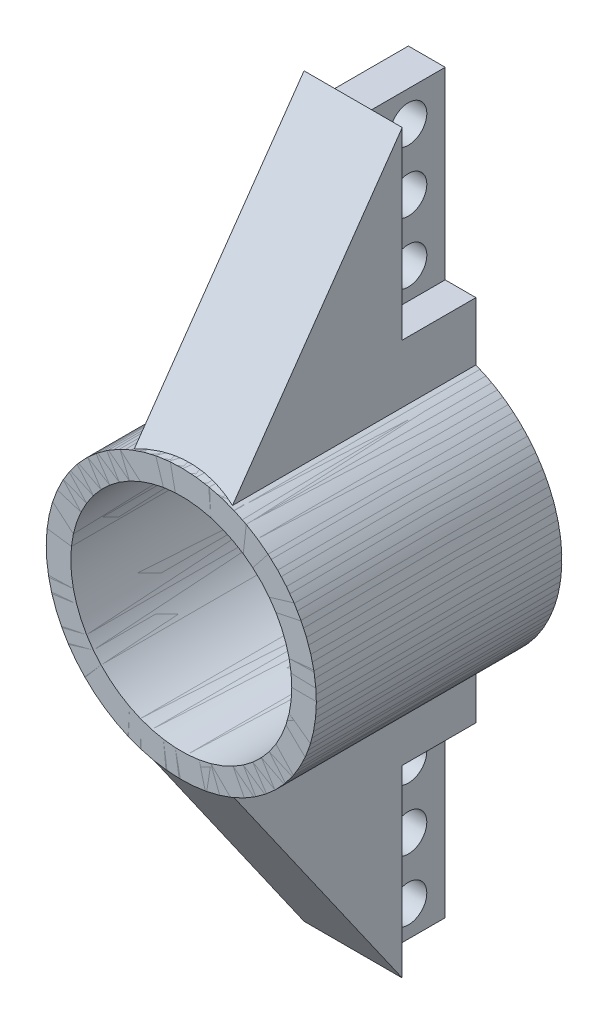
SolidWorks part; units mm, degrees
ref_plane "Front Plane" through (0, 0, 0) normal (0, 0, 1) x (1, 0, 0)
ref_plane "Top Plane" through (0, 0, 0) normal (0, 1, 0) x (1, 0, 0)
ref_plane "Right Plane" through (0, 0, 0) normal (1, 0, 0) x (0, 0, -1)
other "Configuration Table"
sketch "Sketch1" plane through (0, 0, 0) normal (0, 0, 1) x (1, 0, 0)
  circle A0 centre (0, 0) radius 9
  circle A1 centre (0, 0) radius 11
  dimension "D1" = 18
  dimension "D2" = 22
extrude "Boss-Extrude1" add sketch "Sketch1" along normal blind 20
sketch "Sketch2" plane through (0, 0, 0) normal (1, 0, 0) x (0, 0, -1)
  line L0 (-20, 10) -> (-20, 6.5)
  line L2 (-20, 6.5) -> (0, 6.5)
  line L3 (-20, 11) -> (-20, -11) construction
  line L5 (0, 6.5) -> (0, 30)
  line L6 (-20, 10) -> (-6, 30)
  line L7 (-6, 30) -> (0, 30)
  dimension "D1" = 30
  dimension "D2" = 6
  dimension "D3" = 10
extrude "Boss-Extrude2" add sketch "Sketch2" along normal mid plane 8
sketch "Sketch3" plane through (0, 30, 0) normal (0, 1, 0) x (1, 0, 0)
  line L0 (-4, 0) -> (-1.5, 0)
  line L1 (4, 0) -> (-4, 0) construction
  line L2 (-1.5, 0) -> (-1.5, -6)
  line L3 (4, -6) -> (-4, -6) construction
  line L4 (-1.5, -6) -> (-4, -6)
  line L5 (-4, -6) -> (-4, 0)
  line L6 (4, 0) -> (1.5, 0)
  line L7 (1.5, 0) -> (1.5, -6)
  line L8 (1.5, -6) -> (4, -6)
  line L9 (4, -6) -> (4, 0)
  dimension "D1" = 2.5
extrude "Cut-Extrude1" cut sketch "Sketch3" against normal blind 15
sketch "Sketch6" plane through (-1.5, 0, 0) normal (-1, 0, 0) x (0, 0, 1)
  circle A1 centre (3, 17.5) radius 1.5
  circle A2 centre (3, 22.5) radius 1.5
  circle A3 centre (3, 27.5) radius 1.5
  dimension "D4" = 5
  dimension "D5" = 5
move or copy body "Body-Move/Copy1" bodies to move or copy 104 copy yes number of copies 1 rotation origin (0, 0, 0) rotation axis (0, 0, 1) rotation angle 180
sketch "Sketch4" plane through (0, 0, 0) normal (0, 0, -1) x (-1, 0, 0)
  circle A0 centre (0, 0) radius 9
extrude "Cut-Extrude2" cut sketch "Sketch4" against normal through all
extrude "Cut-Extrude3" cut sketch "Sketch6" against normal through all
sketch "Sketch7" plane through (-1.5, 0, 0) normal (-1, 0, 0) x (0, 0, 1)
  circle A1 centre (3, -17.5) radius 1.5
  circle A2 centre (3, -22.5) radius 1.5
  circle A3 centre (3, -27.5) radius 1.5
  dimension "D4" = 5
  dimension "D5" = 5
extrude "Cut-Extrude4" cut sketch "Sketch7" against normal through all
